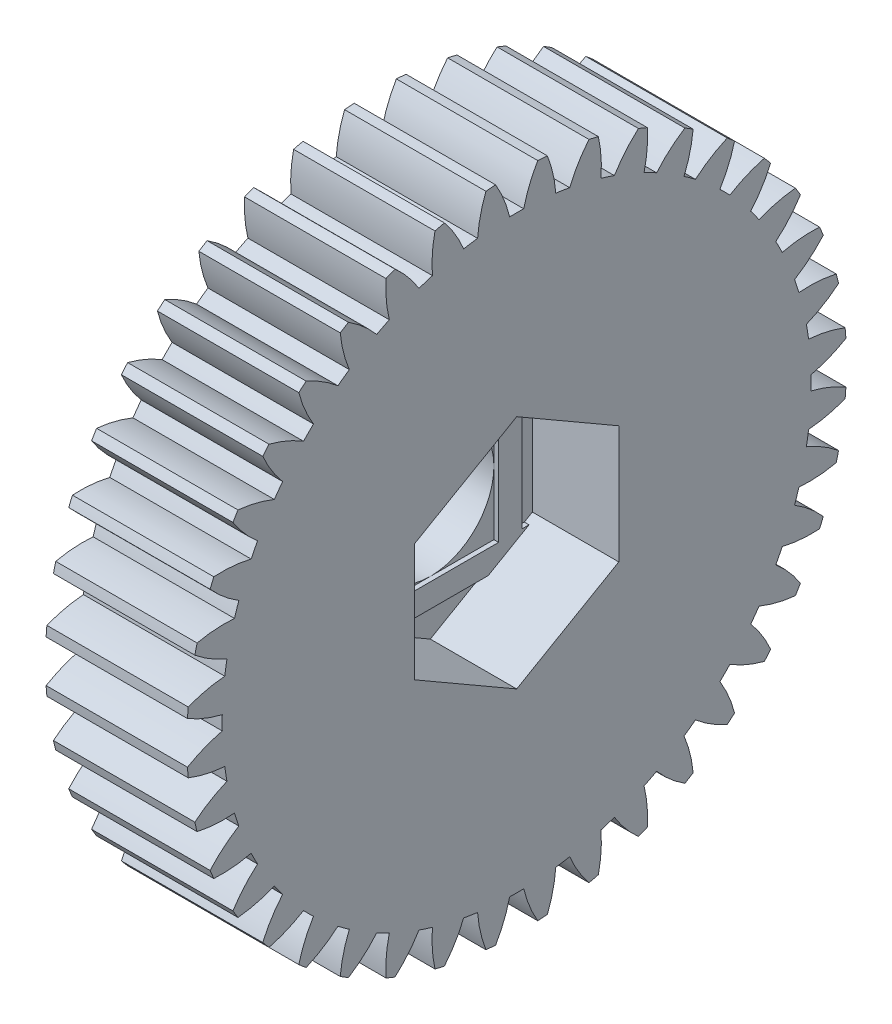
SolidWorks part; units mm, degrees
ref_plane "Plane1" through (0, 0, 0) normal (0, 0, 1) x (1, 0, 0)
ref_plane "Plane2" through (0, 0, 0) normal (0, 1, 0) x (1, 0, 0)
ref_plane "Plane3" through (0, 0, 0) normal (1, 0, 0) x (0, 0, -1)
sketch "HoldingSke" plane through (0, 0, 0) normal (0, 1, 0) x (1, 0, 0)
  line L0 (0, 0) -> (0.766, -0.6428)
  line L1 (-15, 0) -> (100, 0) construction
  line L2 (0, 0) -> (-2.1039, 2.3779)
  line L3 (0, 0) -> (-11.863, 4.5341)
  line L4 (0, 0) -> (6.6156, 5.5511)
  line L5 (0, 0) -> (-46.8476, -17.4728)
  line L6 (0, 0) -> (-7.4607, -5.0337)
  line L7 (-2.1039, 2.3779) -> (8.6586, 51.2059)
  line L8 (-76.2, 54.61) -> (-75.5, 54.61)
  line L9 (-71.009, 38.7566) -> (-53.1078, 45.2721)
  line L10 (-76.2, 71.12) -> (104.1128, 71.12)
  line L11 (0, 0) -> (-9, 0)
  line L12 (-76.2, 101.6) -> (-76.162, 101.6)
  line L13 (24.9733, 27.94) -> (52.9518, 28.4284)
  line L14 (24.9733, 27.94) -> (24.9743, 27.94)
  line L15 (24.9733, 27.94) -> (100.4006, 29.5858)
  line L16 (-63.627, -1) -> (-12.827, -1)
  circle A0 centre (0, 0) radius 2
  circle A1 centre (0, 0) radius 18.749
  circle A2 centre (0, 0) radius 37.5
  circle A3 centre (0, 0) radius 2
  dimension "MHD" = 37.498
  dimension "Hub_dia" = 75
  dimension "Bore" = 4
  dimension "MBD" = 4
  dimension "Num_teeth" = 40
  dimension "Pitch" = 1
  dimension "Overall_len" = 50
  dimension "Show_teeth" = 40
  dimension "Thickness" = 9
  dimension "OAL" = 50.0001
  dimension "T_dim" = 0.7
  dimension "Ap" = 20
  dimension "H" = 19.05
  dimension "Pitch_radius" = 180.3128
  dimension "Width" = 9
  dimension "Backlash" = 0.038
  dimension "Addendum_fac" = 1
  dimension "Dedendum_fac" = 1.25
  dimension "Clearance_fac" = 0.25
  dimension "Dedendum_add" = 0.001
  dimension "Module" = 1
sketch "BasProSke" plane through (0, 0, 0) normal (0, 1, 0) x (1, 0, 0)
  line L0 (-10, 0) -> (60, 0) construction
  line L1 (0, 0) -> (0, 21)
  line L2 (0, 0) -> (9, 0)
  line L3 (9, 0) -> (9, 21)
  line L4 (9, 21) -> (0, 21)
  dimension "Thickness" = 9
  dimension "Diameter" = 42
revolve "Base-Revolve" add sketch "BasProSke" angle 360 about L0
sketch "TooCutSke" plane through (0, 0, 0) normal (1, 0, 0) x (0, 0, -1)
  line L1 (0, 0) -> (0, 107) construction
  line L2 (0, 0) -> (-0.8517, 19.9819) construction
  line L3 (0, 0) -> (-3.1363, 39.8509) construction
  line L4 (-0.8517, 19.9819) -> (-1.5682, 19.9255) construction
  arc A0 (0.4487, 18.7436) -> (-0.4487, 18.7436) centre (0, 0) ccw
  arc A1 (1.3547, 20.9817) -> (-1.3547, 20.9817) centre (0, 0) ccw
  circle A2 centre (0, 0) radius 20 construction
  circle A3 centre (0, 0) radius 18.7939 construction
  arc A4 (-0.4487, 18.7436) -> (-1.3547, 20.9817) centre (-8.2322, 16.895) ccw
  arc A5 (1.3547, 20.9817) -> (0.4487, 18.7436) centre (8.2322, 16.895) ccw
  dimension "Root_dia" = 37.498
  dimension "Overcut_dia" = 42.0508
  dimension "Pitch_dia" = 40
  dimension "Base_dia" = 37.5877
  dimension "Flank_rad" = 8
  dimension "Half_ang" = 4.5
  dimension "Half_CT" = 0.7187
extrude "ToothCut" cut sketch "TooCutSke" along normal through all
fillet "Breaks" [suppressed] radius 0.02 tangent propagation no
fillet "RootFillets" [suppressed] radius 0.251
pattern_circular "TeethCuts" count 40 every 9 about axis through (-10, 0, 0) along (1, 0, 0) of "ToothCut", "RootFillets", "Breaks"
sketch "HubNeaOneSke" plane through (0, 0, 0) normal (-1, 0, 0) x (0, 0, 1)
  circle A0 centre (0, 0) radius 18.749
  dimension "Diameter" = 37.498
extrude "HubNearOne" [suppressed] add sketch "HubNeaOneSke" along normal blind 41.0001
sketch "HubNeaBotSke" plane through (0, 0, 0) normal (-1, 0, 0) x (0, 0, 1)
  circle A0 centre (0, 0) radius 18.749
  dimension "Diameter" = 37.498
extrude "HubNearBoth" [suppressed] add sketch "HubNeaBotSke" along normal blind 20.5
ref_plane "FarPln" through (9, 0, 0) normal (1, 0, 0) x (0, 0, -1)
sketch "HubFarSke" plane through (9, 0, 0) normal (1, 0, 0) x (0, 0, -1)
  circle A0 centre (0, 0) radius 18.749
  dimension "Diameter" = 37.498
extrude "HubFar" [suppressed] add sketch "HubFarSke" along normal blind 20.5
sketch "BorSke" plane through (0, 0, 0) normal (1, 0, 0) x (0, 0, -1)
  circle A0 centre (0, 0) radius 2
  dimension "Diameter" = 4
extrude "Bore" cut sketch "BorSke" along normal mid plane 100.0001
sketch "KeySke" plane through (0, 0, 0) normal (1, 0, 0) x (0, 0, -1)
  line L0 (-0.8, 0) -> (-0.8, 2.7)
  line L1 (-0.8, 2.7) -> (0.8, 2.7)
  line L2 (0.8, 2.7) -> (0.8, 0)
  line L3 (0, 0) -> (0, 34) construction
  line L4 (-0.8, 0) -> (0.8, 0)
  dimension "Offset" = 2.7
  dimension "Width" = 1.6
extrude "Keyway" [suppressed] cut sketch "KeySke" along normal mid plane 100.0001
pattern_circular "Keyway2" [suppressed] count 2 every 90 about axis through (-10, 0, 0) along (1, 0, 0) reverse direction yes
sketch "Sketch1" plane through (9, 0, 0) normal (1, 0, 0) x (0, 0, -1)
  line L1 (0, 7.5056) -> (-6.5, 3.7528)
  line L2 (-6.5, 3.7528) -> (-6.5, -3.7528)
  line L3 (-6.5, -3.7528) -> (0, -7.5056)
  line L4 (0, -7.5056) -> (6.5, -3.7528)
  line L5 (6.5, -3.7528) -> (6.5, 3.7528)
  line L6 (6.5, 3.7528) -> (0, 7.5056)
  circle A0 centre (0, 0) radius 7.5056
  circle A2 centre (0, 0) radius 6.5 construction
  circle A3 centre (0, 0) radius 4.05
  dimension "D1" = 8.1
  dimension "D2" = 13
extrude "Cut-Extrude1" cut sketch "Sketch1" against normal blind 5.5 contours L1 L2 L3 L4 L5 L6
extrude "Cut-Extrude2" cut sketch "Sketch1<7>" against normal through all contours A3 region at (9, 0, 0)
sketch "Sketch1<7>" plane through (9, 0, 0) normal (1, 0, 0) x (0, 0, -1) same geometry as "Sketch1"
sketch "Sketch2" plane through (0, 0, 0) normal (-1, 0, 0) x (0, 0, 1)
  circle A0 centre (0, 0) radius 6
  circle A1 centre (0, 0) radius 4
  dimension "D1" = 12
  dimension "D2" = 8
extrude "Boss-Extrude1" add sketch "Sketch2" along normal blind 2.3
sketch "Sketch3" plane through (3.5, 0, 0) normal (1, 0, 0) x (0, 0, -1)
  line L1 (4.05, 4.05) -> (-4.05, 4.05)
  line L2 (4.05, 4.05) -> (4.05, -4.05)
  line L3 (4.05, -4.05) -> (-4.05, -4.05)
  line L4 (-4.05, 4.05) -> (-4.05, -4.05)
  line L6 (5.55, 5.55) -> (5.55, -5.55)
  line L7 (5.55, -5.55) -> (-5.55, -5.55)
  line L8 (-5.55, 5.55) -> (-5.55, -5.55)
  line L9 (5.55, 5.55) -> (-5.55, 5.55)
  line L10 (5.55, 4.05) -> (5.9852, 4.05)
  line L11 (6.5, 3.7528) -> (0, 7.5056) construction
  line L12 (5.55, -4.05) -> (5.9852, -4.05)
  line L13 (0, -7.5056) -> (6.5, -3.7528) construction
  line L14 (-5.55, -4.05) -> (-5.9852, -4.05)
  line L15 (-6.5, -3.7528) -> (0, -7.5056) construction
  line L16 (-5.55, 4.05) -> (-5.9852, 4.05)
  line L17 (0, 7.5056) -> (-6.5, 3.7528) construction
  circle A0 centre (0, 0) radius 4.05 construction
  line M10 (6.5, 3.7528) -> (0, 7.5056)
  line M11 (0, 7.5056) -> (-6.5, 3.7528)
  line M13 (-6.5, -3.7528) -> (0, -7.5056)
  line M14 (0, -7.5056) -> (6.5, -3.7528)
  dimension "D1" = 1.5
extrude "Boss-Extrude2" add sketch "Sketch3" along normal blind 0.3 contours L9 L8 L7 L6 L4 L1 L2 L3 M10 M11 M13 M14 | L12 L6 M14 | L6 L10 M10 | L16 L8 M11 | L8 L14 M13 region at (3.5, 0, -5.393) region at (3.5, 4.1338, -5.6951) region at (3.5, -4.1338, -5.6951) region at (3.5, 4.1338, 5.6951) region at (3.5, -4.1338, 5.6951)
equation "' \"Module@HoldingSke\" = 6.35"
equation "' \"Num_teeth@HoldingSke\" = 12"
equation "' \"Ap@HoldingSke\" =  20"
equation "' \"Ap@HoldingSke\" = 20"
equation "' \"Width@HoldingSke\" = 0.5 * 25.4"
equation "' \"Hub_dia@HoldingSke\"= 1 * 25.4"
equation "' \"Hub_dia@HoldingSke\" = 1 * 25.4"
equation "' \"Overall_len@HoldingSke\" = 1.0 * 25.4"
equation "' \"Bore@HoldingSke\" = 0.75 * 25.4"
equation "' \"T_dim@HoldingSke\" = 0.1 * 25.4"
equation "' \"Width@KeySke\" = 0.25 * 25.4"
equation "' \"Show_teeth@HoldingSke\" = 13"
equation "' \"Backlash@HoldingSke\" = 0.009 * 25.4"
equation "' \"Addendum_fac@HoldingSke\" = 1.0"
equation "' \"Dedendum_fac@HoldingSke\" = 1.25"
equation "' \"Dedendum_add@HoldingSke\" = 0.00005 * 25.4"
equation "' \"Clearance_fac@HoldingSke\" = 0.25"
equation "\"Pitch@HoldingSke\" = 1 / \"Module@HoldingSke\""
equation "\"Overcut_dia@TooCutSke\" = (\"Num_teeth@HoldingSke\" + 2 * \"Addendum_fac@HoldingSke\") / \"Pitch@HoldingSke\" + 0.002 * 25.4"
equation "\"Pitch_dia@TooCutSke\" = \"Num_teeth@HoldingSke\" / \"Pitch@HoldingSke\""
equation "\"Base_dia@TooCutSke\" = \"Num_teeth@HoldingSke\" / \"Pitch@HoldingSke\" * cos((\"Ap@HoldingSke\"  * 3.14159265 / 180))"
equation "\"Root_dia@TooCutSke\" = (\"Num_teeth@HoldingSke\" + 2) / \"Pitch@HoldingSke\" - 2 * (\"Addendum_fac@HoldingSke\" + \"Dedendum_fac@HoldingSke\") / \"Pitch@HoldingSke\" - \"Dedendum_add@HoldingSke\" * 2"
equation "\"Half_ang@TooCutSke\" = 180 / \"Num_teeth@HoldingSke\""
equation "\"Half_CT@TooCutSke\" = \"Num_teeth@HoldingSke\" / \"Pitch@HoldingSke\" * sin((3.14159265 / 2 / \"Num_teeth@HoldingSke\")) / 2 - 7 * \"Backlash@HoldingSke\" / 4"
equation "\"Flank_rad@TooCutSke\" = \"Num_teeth@HoldingSke\" / \"Pitch@HoldingSke\" / 5"
equation "\"Radius@RootFillets\" = \"Clearance_fac@HoldingSke\" / \"Pitch@HoldingSke\" + \"Dedendum_add@HoldingSke\""
equation "\"Break_rad@Breaks\" = 0.02 / \"Pitch@HoldingSke\""
equation "\"Thickness@HoldingSke\" = \"Width@HoldingSke\""
equation "\"OAL@HoldingSke\" = \"Thickness@HoldingSke\""
equation "\"MHD@HoldingSke\" = (\"Num_teeth@HoldingSke\" + 2) / \"Pitch@HoldingSke\" - 2 * (\"Addendum_fac@HoldingSke\" + \"Dedendum_fac@HoldingSke\")  / \"Pitch@HoldingSke\" - \"Dedendum_add@HoldingSke\" * 2"
equation "\"MBD@HoldingSke\" = (\"Num_teeth@HoldingSke\" + 2) / \"Pitch@HoldingSke\" - 2 * (\"Addendum_fac@HoldingSke\" + \"Dedendum_fac@HoldingSke\")  / \"Pitch@HoldingSke\" - \"Dedendum_add@HoldingSke\" * 2 - 0.002 * 25.4"
equation "\"MHD@HoldingSke\" = ((sgn( \"MHD@HoldingSke\" - \"Hub_dia@HoldingSke\" )-1)*( \"MHD@HoldingSke\" - \"Hub_dia@HoldingSke\" ))/-2+ \"Hub_dia@HoldingSke\""
equation "\"MBD@HoldingSke\" = ((sgn( \"MBD@HoldingSke\" - \"Bore@HoldingSke\" )-1)*( \"MBD@HoldingSke\" - \"Bore@HoldingSke\" ))/-2+ \"Bore@HoldingSke\""
equation "\"OAL@HoldingSke\" = ((sgn( \"OAL@HoldingSke\" - \"Overall_len@HoldingSke\" )+1)*( \"OAL@HoldingSke\" - \"Overall_len@HoldingSke\" ))/2 + \"Overall_len@HoldingSke\" + 0.000002 * 25.4"
equation "\"Num_teeth@TeethCuts\" = int( \"Show_teeth@HoldingSke\" ) + 1"
equation "\"Num_teeth@TeethCuts\" = ((sgn( \"Num_teeth@TeethCuts\" - \"Num_teeth@HoldingSke\" )-1)*( \"Num_teeth@TeethCuts\" - \"Num_teeth@HoldingSke\" ))/-2+ \"Num_teeth@HoldingSke\""
equation "\"Num_teeth@TeethCuts\" = ((sgn( \"Num_teeth@TeethCuts\" - 2.0)+1)*( \"Num_teeth@TeethCuts\" - 2.0))/2 +2.0"
equation "\"Angle@TeethCuts\" = 360.0 / \"Num_teeth@HoldingSke\""
equation "\"Diameter@BasProSke\" = (\"Num_teeth@HoldingSke\" + 2 * \"Addendum_fac@HoldingSke\") / \"Pitch@HoldingSke\""
equation "\"Thickness@BasProSke\"  = \"Thickness@HoldingSke\""
equation "' \"Fillet_rad@BasProSke\" =  \"Thickness@HoldingSke\" * 0.05"
equation "' \"Fillet_rad@BasProSke\" = \"Thickness@HoldingSke\" * 0.05"
equation "\"MHD@HoldingSke\" = ((sgn( \"MHD@HoldingSke\" - \"Root_dia@TooCutSke\" )-1)*( \"MHD@HoldingSke\" - \"Root_dia@TooCutSke\" ))/-2+ \"Root_dia@TooCutSke\""
equation "\"Diameter@HubNeaOneSke\" = \"MHD@HoldingSke\""
equation "\"Length@HubNearOne\" = \"OAL@HoldingSke\" - \"Thickness@BasProSke\""
equation "\"Diameter@HubNeaBotSke\" = \"MHD@HoldingSke\""
equation "\"Length@HubNearBoth\" = ( \"OAL@HoldingSke\" - \"Thickness@BasProSke\" ) / 2.0"
equation "\"Thickness@FarPln\" = \"Thickness@BasProSke\""
equation "\"Diameter@HubFarSke\" = \"MHD@HoldingSke\""
equation "\"Length@HubFar\" = ( \"OAL@HoldingSke\" - \"Thickness@BasProSke\" ) / 2.0"
equation "\"Diameter@BorSke\" = \"MBD@HoldingSke\""
equation "\"D1@Bore\" = \"OAL@HoldingSke\" * 2.0"
equation "\"D1@Keyway\" = \"OAL@HoldingSke\" * 2.0"
equation "\"Offset@KeySke\" = \"T_dim@HoldingSke\" + \"MBD@HoldingSke\" / 2.0"
